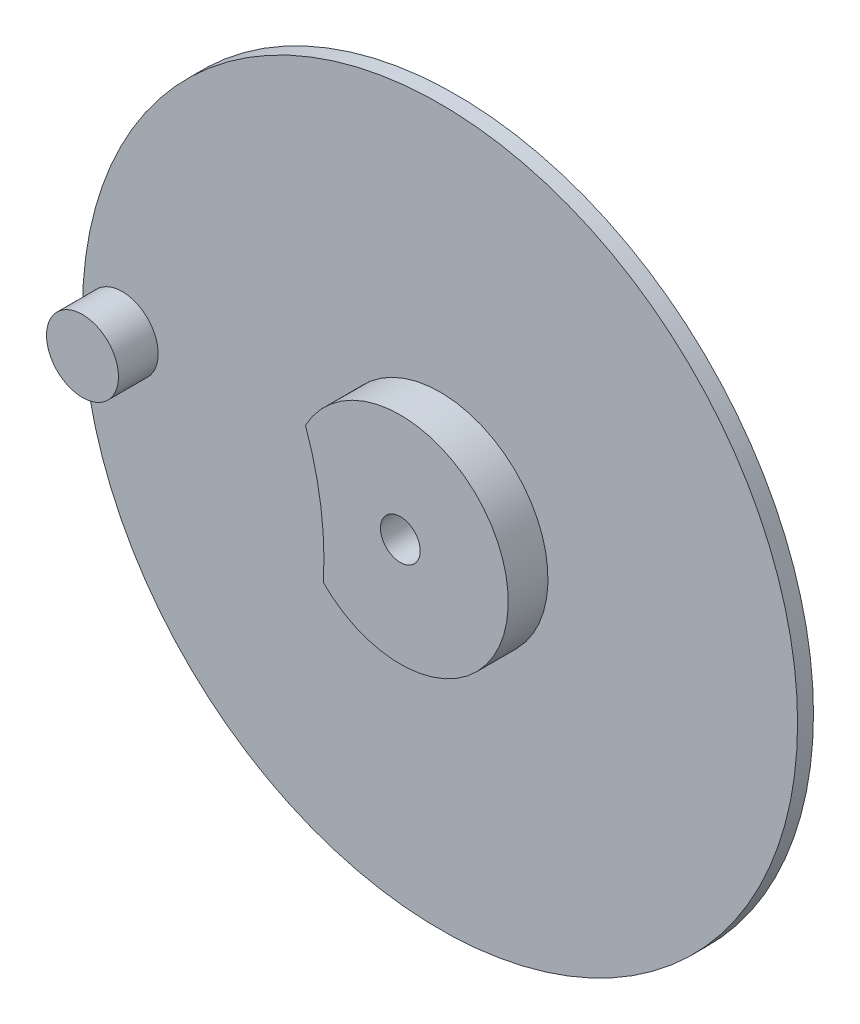
SolidWorks part; units mm, degrees
ref_plane "前视基准面" through (0, 0, 0) normal (0, 0, 1) x (1, 0, 0)
ref_plane "上视基准面" through (0, 0, 0) normal (0, 1, 0) x (1, 0, 0)
ref_plane "右视基准面" through (0, 0, 0) normal (1, 0, 0) x (0, 0, -1)
other "Configuration Table"
sketch "草图1" plane through (0, 0, 0) normal (0, 0, 1) x (1, 0, 0)
  line L0 (-2.5297, 2.5297) -> (-3.6261, 3.6261) construction
  line L1 (0, 0) -> (-0.7637, 0.7637) construction
  circle A0 centre (0, 0) radius 0.1987
  circle A1 centre (0, 0) radius 3.5775
  arc A3 (-0.7705, -0.7568) -> (-0.949, 0.5156) centre (0, 0) ccw
  circle A4 centre (-3.18, 0) radius 0.36
  arc A5 (-0.7705, -0.7568) -> (-0.949, 0.5156) centre (-3.944, -0.5532) ccw
  dimension "D1" = 1.08
  dimension "D2" = 0.3975
  dimension "D5" = 0.72
extrude "凸台-拉伸2" add sketch "草图1" against normal blind 0.159 contours A5 A3 A0 | A1 A4 A3 A5 | A4 region at (-3.5674, 0, 0) region at (-0.7655, -0.1074, 0) region at (-3.18, 0, 0)
extrude "凸台-拉伸3" add sketch "草图1<6>" along normal blind 0.3975 contours A5 A3 A0 | A4 region at (-0.7655, -0.1074, 0) region at (-3.18, 0, 0)
sketch "草图1<6>" plane through (0, 0, 0) normal (0, 0, 1) x (1, 0, 0) same geometry as "草图1"
scale "缩放比例3" bodies to scale 109 scale about centroid uniform scaling yes scale factor 25
